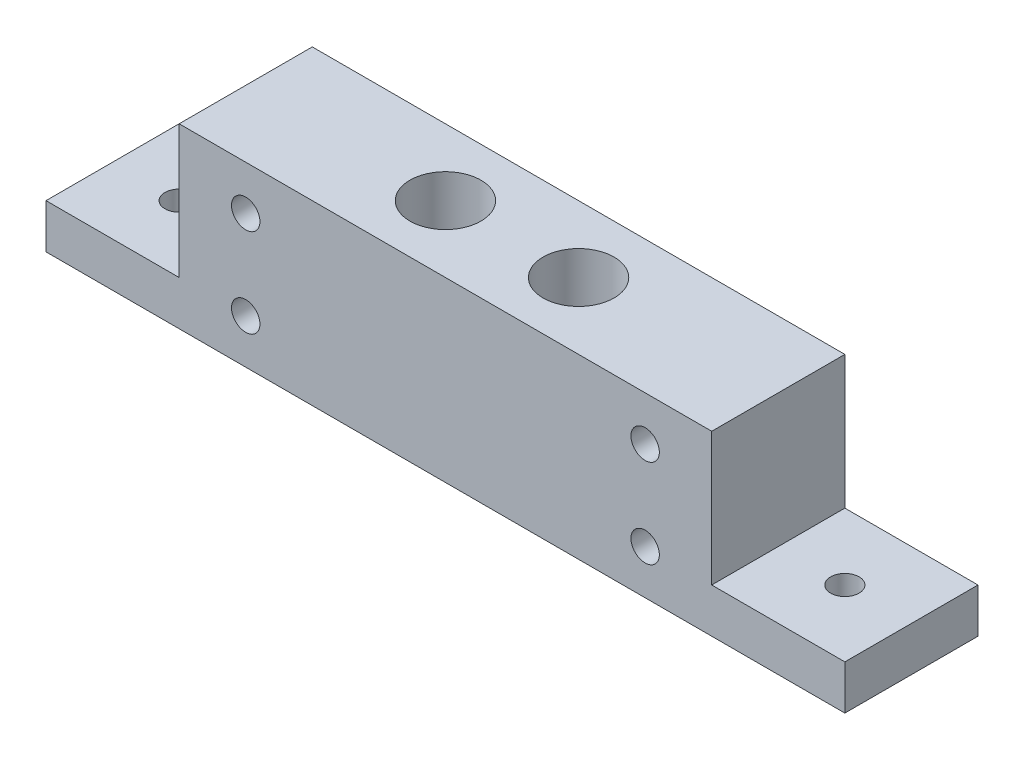
SolidWorks part; units mm, degrees
ref_plane "Front Plane" through (0, 0, 0) normal (0, 0, 1) x (1, 0, 0)
ref_plane "Top Plane" through (0, 0, 0) normal (0, 1, 0) x (1, 0, 0)
ref_plane "Right Plane" through (0, 0, 0) normal (1, 0, 0) x (0, 0, -1)
sketch "Sketch2" plane through (0, 0, 0) normal (0, 1, 0) x (1, 0, 0)
  line L0 (0, 0) -> (-7.5, 0) construction
  line L1 (0, 0) -> (7.5, 0) construction
  line L3 (15, -7.5) -> (-15, -7.5)
  line L4 (15, -7.5) -> (15, 7.5)
  line L5 (15, 7.5) -> (-15, 7.5)
  line L6 (-15, -7.5) -> (-15, 7.5)
  line L7 (15, -7.5) -> (-15, 7.5) construction
  line L8 (15, 7.5) -> (-15, -7.5) construction
  line L9 (-15, 7.5) -> (-30, 7.5)
  line L10 (-15, 7.5) -> (-15, -7.5)
  line L11 (-15, -7.5) -> (-30, -7.5)
  line L12 (-30, 7.5) -> (-30, -7.5)
  line L13 (15, 7.5) -> (30, 7.5)
  line L14 (15, 7.5) -> (15, -7.5)
  line L15 (15, -7.5) -> (30, -7.5)
  line L16 (30, 7.5) -> (30, -7.5)
  circle A0 centre (-7.5, 0) radius 4
  circle A1 centre (7.5, 0) radius 4
  dimension "D3" = 8
  dimension "D4" = 8
  dimension "D1" = 7.5
  dimension "D2" = 7.5
  dimension "D5" = 15
  dimension "D6" = 30
  dimension "D7" = 15
  dimension "D8" = 15
  dimension "D9" = 15
  dimension "D10" = 15
extrude "Boss-Extrude1" add sketch "Sketch2" along normal blind 10 contours L9 L12 L11 L6 | L6 L3 L4 L5 A1 A0 | L16 L13 L4 L15 region at (0, 0, 0) region at (22.5, 0, 0) region at (-22.5, 0, 0)
extrude "Boss-Extrude2" add sketch "Sketch2<3>" against normal blind 10 contours L9 L12 L11 L6 | L6 L3 L4 L5 A1 A0 | A0 | A1 | L16 L13 L4 L15 region at (0, 0, 0) region at (22.5, 0, 0) region at (-22.5, 0, 0) region at (-7.5, 0, 0) region at (7.5, 0, 0)
sketch "Sketch2<3>" plane through (0, 0, 0) normal (0, 1, 0) x (1, 0, 0) same geometry as "Sketch2"
sketch "Sketch4" plane through (0, 0, 7.5) normal (0, 0, 1) x (1, 0, 0)
  line L0 (-30, 0) -> (-22.5, 0) construction
  line L1 (-30, 10) -> (-30, -10) construction
  line L2 (30, 0) -> (22.5, 0) construction
  line L3 (30, 10) -> (30, -10) construction
  line L4 (-22.5, -5) -> (-22.5, 5) construction
  line L5 (22.5, -5) -> (22.5, 5) construction
  line L7 (-22.5, 8.4352) -> (-25.475, 6.7176)
  line L8 (-25.475, 6.7176) -> (-25.475, 3.2824)
  line L9 (-25.475, 3.2824) -> (-22.5, 1.5648)
  line L10 (-22.5, 1.5648) -> (-19.525, 3.2824)
  line L11 (-19.525, 3.2824) -> (-19.525, 6.7176)
  line L12 (-19.525, 6.7176) -> (-22.5, 8.4352)
  line L13 (22.5, 8.4352) -> (19.525, 6.7176)
  line L14 (19.525, 6.7176) -> (19.525, 3.2824)
  line L15 (19.525, 3.2824) -> (22.5, 1.5648)
  line L16 (22.5, 1.5648) -> (25.475, 3.2824)
  line L17 (25.475, 3.2824) -> (25.475, 6.7176)
  line L18 (25.475, 6.7176) -> (22.5, 8.4352)
  line L19 (-22.5, -8.4352) -> (-19.525, -6.7176)
  line L20 (22.5, -8.4352) -> (25.475, -6.7176)
  line L21 (25.475, -6.7176) -> (25.475, -3.2824)
  line L22 (25.475, -3.2824) -> (22.5, -1.5648)
  line L23 (22.5, -1.5648) -> (19.525, -3.2824)
  line L24 (19.525, -3.2824) -> (19.525, -6.7176)
  line L25 (19.525, -6.7176) -> (22.5, -8.4352)
  line L26 (-19.525, -6.7176) -> (-19.525, -3.2824)
  line L27 (-19.525, -3.2824) -> (-22.5, -1.5648)
  line L28 (-22.5, -1.5648) -> (-25.475, -3.2824)
  line L29 (-25.475, -3.2824) -> (-25.475, -6.7176)
  line L30 (-25.475, -6.7176) -> (-22.5, -8.4352)
  circle A0 centre (22.5, 5) radius 1.6
  circle A1 centre (22.5, -5) radius 1.6
  circle A2 centre (-22.5, -5) radius 1.6
  circle A3 centre (-22.5, 5) radius 1.6
  circle A4 centre (-22.5, 5) radius 2.975 construction
  circle A5 centre (22.5, 5) radius 2.975 construction
  circle A6 centre (22.5, -5) radius 2.975 construction
  circle A7 centre (-22.5, -5) radius 2.975 construction
  point P12 (-22.5, 0)
  point P15 (22.5, 0)
  dimension "D5" = 3.2
  dimension "D6" = 3.2
  dimension "D7" = 3.2
  dimension "D8" = 3.2
  dimension "D9" = 5.95
  dimension "D10" = 5.95
  dimension "D11" = 5.95
  dimension "D12" = 5.95
  dimension "D1" = 7.5
  dimension "D2" = 7.5
  dimension "D3" = 10
  dimension "D4" = 10
extrude "Cut-Extrude1" cut sketch "Sketch4" against normal through all contours A2 | A3 | A0 | A1 region at (22.5, 5, 7.5) region at (22.5, -5, 7.5) region at (-22.5, -5, 7.5) region at (-22.5, 5, 7.5)
extrude "Cut-Extrude2" cut sketch "Sketch4<3>" against normal blind 2.5 from offset 6.25 offset against normal yes
sketch "Sketch4<3>" plane through (0, 0, 7.5) normal (0, 0, 1) x (1, 0, 0) same geometry as "Sketch4"
sketch "Sketch5" plane through (0, -10, 0) normal (0, -1, 0) x (1, 0, 0)
  line L1 (-30, 7.5) -> (-45, 7.5)
  line L2 (-30, 7.5) -> (-30, -7.5)
  line L3 (-30, -7.5) -> (-45, -7.5)
  line L4 (-45, 7.5) -> (-45, -7.5)
  line L5 (30, 7.5) -> (45, 7.5)
  line L6 (30, 7.5) -> (30, -7.5)
  line L7 (30, -7.5) -> (45, -7.5)
  line L8 (45, 7.5) -> (45, -7.5)
  dimension "D1" = 15
  dimension "D2" = 15
extrude "Boss-Extrude3" add sketch "Sketch5" against normal blind 5
sketch "Sketch6" plane through (0, -10, 0) normal (0, -1, 0) x (1, 0, 0)
  line L0 (-45, 7.5) -> (-30, -7.5) construction
  line L1 (45, -7.5) -> (-45, -7.5) construction
  line L2 (0, 0) -> (0, 7.5) construction
  line L3 (45, 7.5) -> (-45, 7.5) construction
  circle A0 centre (-37.5, 0) radius 1.6
  circle A1 centre (37.5, 0) radius 1.6
  dimension "D1" = 3.2
extrude "Cut-Extrude3" cut sketch "Sketch6" against normal up to next
